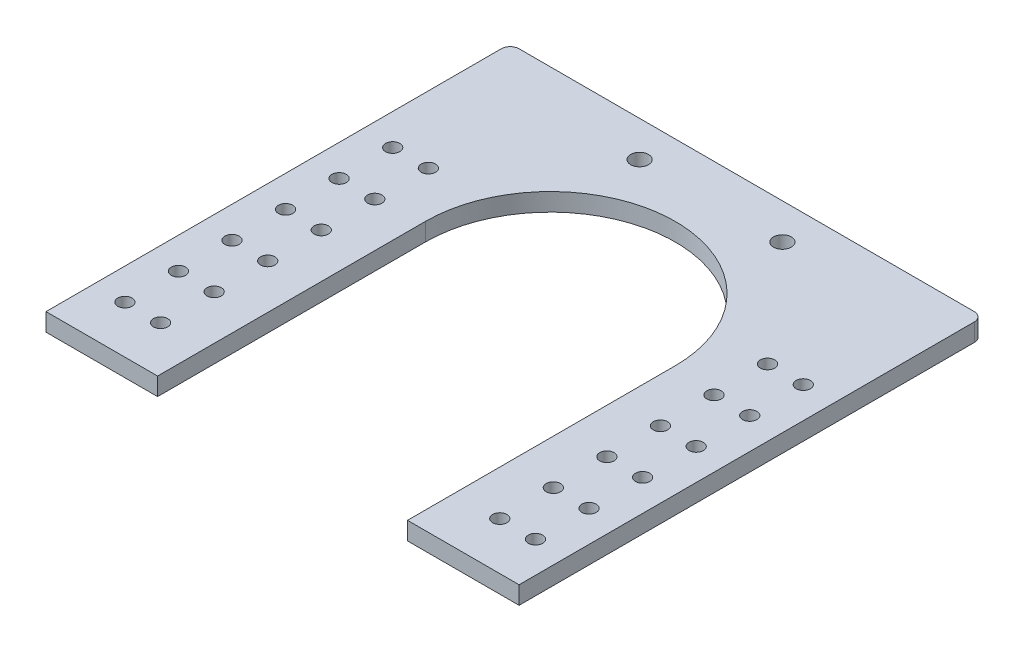
SolidWorks part; units mm, degrees
ref_plane "Front" through (0, 0, 0) normal (0, 0, 1) x (1, 0, 0)
ref_plane "Top" through (0, 0, 0) normal (0, 1, 0) x (1, 0, 0)
ref_plane "Right" through (0, 0, 0) normal (1, 0, 0) x (0, 0, -1)
sketch "Sketch1" plane through (0, 0, 0) normal (0, 1, 0) x (1, 0, 0)
  line L1 (-84.1375, -82.55) -> (84.1375, -82.55)
  line L2 (-84.1375, -82.55) -> (-84.1375, 82.55)
  line L3 (-84.1375, 82.55) -> (84.1375, 82.55)
  line L4 (84.1375, -82.55) -> (84.1375, 82.55)
  line L5 (-84.1375, -82.55) -> (84.1375, 82.55) construction
  line L6 (-84.1375, 82.55) -> (84.1375, -82.55) construction
  point P0 (0, 0)
  dimension "D1" = 168.275
  dimension "D2" = 165.1
extrude "Boss-Extrude1" add sketch "Sketch1" along normal mid plane 6.35 contours L3 L4 L1 L2
sketch "Sketch2" plane through (0, 3.175, 0) normal (0, 1, 0) x (1, 0, 0)
  line L0 (0, -50) -> (0, 50) construction
  line L1 (-84.1375, 82.55) -> (84.1375, 82.55) construction
  line L2 (44.45, 12.7) -> (44.45, -82.55)
  line L3 (-84.1375, -82.55) -> (84.1375, -82.55) construction
  line L4 (44.45, -82.55) -> (-44.45, -82.55)
  line L5 (-44.45, -82.55) -> (-44.45, 12.7)
  circle A0 centre (0, 12.7) radius 44.45
  point P4 (0, 57.15)
  line M2 (-84.1375, -82.55) -> (84.1375, -82.55)
  dimension "D2" = 88.9
  dimension "D1" = 25.4
extrude "Cut-Extrude1" cut sketch "Sketch2" against normal up to next contours A0 | A0 L5 L2 M2 region at (0, 3.175, -12.7) region at (0, 3.175, 51.5649)
sketch "Sketch3" plane through (0, 3.175, 0) normal (0, 1, 0) x (1, 0, 0)
  line L0 (-25.4, 69.85) -> (25.4, 69.85) construction
  line L1 (0, -50) -> (0, 50) construction
  line L2 (-84.1375, 82.55) -> (84.1375, 82.55) construction
  point P0 (-25.4, 69.85)
  point P1 (25.4, 69.85)
  point P4 (0, 69.85)
  dimension "D1" = 50.8
  dimension "D2" = 12.7
hole_wizard "1/4 (0.25) Diameter Hole1" positions "Sketch4" profile "Sketch6" hole size "1/4" standard "ANSI Inch"
sketch "Sketch4" plane through (0, 3.175, 0) normal (0, 1, 0) x (1, 0, 0)
  point P0 (-25.4, 69.85)
  point P3 (25.4, 69.85)
sketch "Sketch6" plane through (-25.4, 3.175, -69.85) normal (1, 0, 0) x (0, 0, 1)
  line L0 (0, 0) -> (0, 27.3077)
  line L1 (0, 27.3077) -> (3.175, 25.4)
  line L2 (3.175, 25.4) -> (3.175, 0)
  line L5 (3.175, 0) -> (0, 0)
  line L10 (0, 27.3077) -> (-3.175, 25.4) construction
  line L11 (0, -6.35) -> (0, 107.95) construction
  dimension "Hole Dia." = 6.35
  dimension "Hole Depth" = 25.4
  dimension "Drill Angle" = 118
sketch "Sketch7" plane through (0, 3.175, 0) normal (0, 1, 0) x (1, 0, 0)
  line L0 (-84.1375, -82.55) -> (-84.1375, 82.55) construction
  point P0 (-73.025, -65.6037)
  point P1 (-60.325, -65.6037)
  dimension "D1" = 11.1125
  dimension "D2" = 12.7
hole_wizard "1/4-20 Tapped Hole1" positions "Sketch8" profile "Sketch10" tap size "1/4-20" standard "ANSI Inch"
sketch "Sketch8" plane through (0, 3.175, 0) normal (0, 1, 0) x (1, 0, 0)
  point P0 (-73.025, -65.6037)
  point P3 (-60.325, -65.6037)
sketch "Sketch10" plane through (-73.025, 3.175, 65.6037) normal (1, 0, 0) x (0, 0, 1)
  line L0 (0, 0) -> (0, 26.9338)
  line L1 (0, 26.9338) -> (2.5527, 25.4)
  line L2 (2.5527, 25.4) -> (2.5527, 0)
  line L5 (2.5527, 0) -> (0, 0)
  line L10 (0, 26.9338) -> (-2.5527, 25.4) construction
  line L11 (0, -6.35) -> (0, 107.95) construction
  dimension "Tap Drill Dia." = 5.1054
  dimension "Tap Drill Depth" = 25.4
  dimension "Drill Angle" = 118
cosmetic thread "Hole Thread1" parameters "D1"=12.7, "D2"=6.35
cosmetic thread "Hole Thread2" parameters "D1"=12.7, "D2"=6.35
pattern_linear "LPattern1" count 6 spacing 19.05 along (0, 0, -1) of "1/4-20 Tapped Hole1"
cosmetic thread "Hole Thread3" parameters "D1"=12.7, "D2"=6.35
cosmetic thread "Hole Thread4" parameters "D1"=12.7, "D2"=6.35
cosmetic thread "Hole Thread5" parameters "D1"=12.7, "D2"=6.35
cosmetic thread "Hole Thread6" parameters "D1"=12.7, "D2"=6.35
cosmetic thread "Hole Thread7" parameters "D1"=12.7, "D2"=6.35
cosmetic thread "Hole Thread8" parameters "D1"=12.7, "D2"=6.35
cosmetic thread "Hole Thread9" parameters "D1"=12.7, "D2"=6.35
cosmetic thread "Hole Thread10" parameters "D1"=12.7, "D2"=6.35
cosmetic thread "Hole Thread11" parameters "D1"=12.7, "D2"=6.35
cosmetic thread "Hole Thread12" parameters "D1"=12.7, "D2"=6.35
mirror "Mirror1" about plane through (0, 0, 0) normal (1, 0, 0) of "LPattern1"
cosmetic thread "Hole Thread13" parameters "D1"=12.7, "D2"=6.35
cosmetic thread "Hole Thread14" parameters "D1"=12.7, "D2"=6.35
cosmetic thread "Hole Thread15" parameters "D1"=12.7, "D2"=6.35
cosmetic thread "Hole Thread16" parameters "D1"=12.7, "D2"=6.35
cosmetic thread "Hole Thread17" parameters "D1"=12.7, "D2"=6.35
cosmetic thread "Hole Thread18" parameters "D1"=12.7, "D2"=6.35
cosmetic thread "Hole Thread19" parameters "D1"=12.7, "D2"=6.35
cosmetic thread "Hole Thread20" parameters "D1"=12.7, "D2"=6.35
cosmetic thread "Hole Thread21" parameters "D1"=12.7, "D2"=6.35
cosmetic thread "Hole Thread22" parameters "D1"=12.7, "D2"=6.35
cosmetic thread "Hole Thread23" parameters "D1"=12.7, "D2"=6.35
cosmetic thread "Hole Thread24" parameters "D1"=12.7, "D2"=6.35
fillet "Fillet1" [suppressed] radius 3.175
fillet "Fillet2" radius 3.175 2 edges at (84.1375, 0, -82.55) (-84.1375, 0, -82.55)
